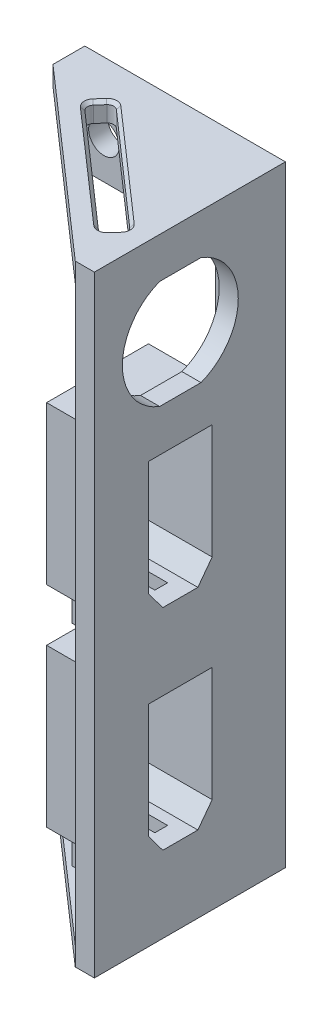
SolidWorks part; units mm, degrees
note: The reader was unsure of these and kept them because the rebuilt part matched: shared geometry of "Sketch4<10>".
ref_plane "Front Plane" through (0, 0, 0) normal (0, 0, 1) x (1, 0, 0)
ref_plane "Top Plane" through (0, 0, 0) normal (0, 1, 0) x (1, 0, 0)
ref_plane "Right Plane" through (0, 0, 0) normal (1, 0, 0) x (0, 0, -1)
sketch "Sketch4" plane through (0, 0, 0) normal (0, 0, 1) x (1, 0, 0)
  line L0 (68.7799, 0) -> (146.409, 0) construction
  line L2 (100.57, 12.5) -> (115.57, 12.5) construction
  line L11 (115.57, -12.5) -> (100.57, -12.5) construction
  line L12 (130.57, -45) -> (130.57, 0)
  line L13 (102.07, -34) -> (125.57, -34)
  line L14 (102.07, -34) -> (102.07, -48)
  line L15 (102.07, -48) -> (121.6669, -48)
  line L17 (121.6669, -48) -> (133.57, -48)
  line L19 (125.57, 0) -> (133.57, 0)
  line L20 (133.57, -48) -> (133.57, 0)
  line L21 (102.07, -45) -> (130.57, -45)
  line L25 (125.57, -34) -> (125.57, 0)
  line L26 (115.57, 12.5) -> (115.57, -12.5) construction
  circle A6 centre (108.07, -40) radius 2.4
  dimension "D1" = 4.8
  dimension "D2" = 3
  dimension "D5" = 6
  dimension "D6" = 6
  dimension "D8" = 5
  dimension "D4" = 5
  dimension "D3" = 3
  dimension "D7" = 10
extrude "Boss-Extrude4" add sketch "Sketch4" along normal blind 3 contours L25 L13 L14 L21 L12 L19 A6
extrude "Boss-Extrude5" add sketch "Sketch4<10>" along normal blind 30 contours L21 L14 L15 L17 L20 L19 L12
sketch "Sketch4<10>" plane through (0, 0, 0) normal (0, 0, 1) x (1, 0, 0) same geometry as "Sketch4"
sketch "Sketch11" plane through (0, -45, 0) normal (0, 1, 0) x (1, 0, 0)
  line L1 (102.07, -3) -> (125.57, -3) construction
  line L3 (130.57, -30) -> (130.57, -3) construction
  line L4 (102.07, -30) -> (130.57, -30) construction
  line L5 (130.57, -30) -> (102.07, -30)
  line L6 (102.07, -30) -> (102.07, -3) construction
  line L7 (102.07, -30) -> (102.07, -3)
  line L8 (130.57, -30) -> (102.07, -5)
  line M4 (102.07, -30) -> (130.57, -30)
  dimension "D1" = 2
extrude "Cut-Extrude2" cut sketch "Sketch11" against normal up to surface (3 mm away) and the other way through all contours L8 L7 M4 up to face at (117.82, -48, 15)
ref_plane "Mirror plane" through (0, 0, 0) normal (0, 1, 0) x (1, 0, 0)
mirror "Mirror2" about plane through (0, 0, 0) normal (0, 1, 0) of "Cut-Extrude2", "Boss-Extrude5", "Boss-Extrude4"
sketch "Socket holes" plane through (130.57, 0, 0) normal (-1, 0, 0) x (0, 0, 1)
  line L0 (11.5, -15) -> (11.5, -33)
  line L1 (11.5, -33) -> (13.75, -36)
  line L2 (13.75, -36) -> (19.25, -36)
  line L3 (19.25, -36) -> (21.5, -33)
  line L4 (21.5, -33) -> (21.5, -15)
  line L5 (21.5, -15) -> (11.5, -15)
  line L6 (16.5, 28.4966) -> (16.5, -28.9107) construction
  line L7 (13.2504, 41.6) -> (19.7496, 41.6)
  line L8 (13.2504, 24.6) -> (19.7496, 24.6)
  line L9 (7.3656, 33.1) -> (29.6735, 33.1) construction
  line L10 (30, 0) -> (24.5, 0) construction
  line L11 (3, -45) -> (3, 45) construction
  line L12 (8.5, -12) -> (8.5, -34)
  line L13 (8.5, -34) -> (12.25, -39)
  line L14 (30, -45) -> (30, 45) construction
  line L15 (3, -34) -> (3, 34) construction
  line L16 (7.833, 24) -> (20.4785, 24) construction
  line L17 (12.25, -39) -> (20.75, -39)
  line L18 (20.75, -39) -> (24.5, -34)
  line L19 (24.5, -34) -> (24.5, -12)
  line L20 (24.5, -12) -> (8.5, -12)
  line L21 (12.25, -39) -> (12.25, -43)
  line L22 (12.25, -43) -> (20.75, -43)
  line L23 (20.75, -43) -> (20.75, -39)
  line L36 (11.5, 0) -> (3, 0) construction
  line L37 (8.5, 21) -> (24.5, 21)
  line L38 (24.5, 21) -> (24.5, -1)
  line L39 (24.5, -1) -> (21.5, -6)
  line L40 (21.5, -6) -> (11.5, -6)
  line L41 (11.5, -6) -> (8.5, -1)
  line L42 (8.5, -1) -> (8.5, 21)
  line L43 (11.5, 18) -> (11.5, 0)
  line L44 (11.5, 0) -> (13.75, -3)
  line L45 (13.75, -3) -> (19.25, -3)
  line L46 (19.25, -3) -> (21.5, 0)
  line L47 (21.5, 0) -> (21.5, 18)
  line L48 (21.5, 18) -> (11.5, 18)
  line L49 (55, 0) -> (-55, 0) construction
  line L50 (11.5, -10) -> (21.5, -10)
  circle A0 centre (16.5, 33.1) radius 9.1
  point P18 (16.5, -36)
  dimension "D2" = 18.2
  dimension "D8" = 24
  dimension "D1" = 10
  dimension "D3" = 17
  dimension "D4" = 21
  dimension "D5" = 18
  dimension "D6" = 5.5
  dimension "D7" = 3
  dimension "D9" = 15
  dimension "D10" = 4
  dimension "D11" = 21
  dimension "D12" = 10
  dimension "D13" = 18
  dimension "D14" = 5.5
  dimension "D15" = 6
  dimension "D16" = 3
  dimension "D17" = 3
  dimension "D18" = 3
  dimension "D19" = 3
  dimension "D20" = 5
  dimension "D21" = 22
  dimension "D22" = 4
extrude "socketholes" cut sketch "Socket holes" against normal up to surface (3 mm away) contours L4 L5 L0 L1 L2 L3 | L7 A0 L8 | L48 L43 L44 L45 L46 L47 up to face at (133.57, 0, 15)
sketch "Sketch12" plane through (0, -48, 0) normal (0, -1, 0) x (1, 0, 0)
  line L0 (130.57, 30) -> (130.57, 0) construction
  line L1 (102.07, 0) -> (133.57, 0) construction
  line L2 (102.07, 5) -> (133.57, 5) construction
  line L3 (133.57, 30) -> (133.57, 0) construction
  line L4 (106.6193, 5) -> (130.57, 26.0094) construction
  line L5 (102.07, 5) -> (130.57, 30) construction
  line L6 (109.6188, 7.6312) -> (128.262, 23.9848)
  line L7 (109.6188, 7.6312) -> (111.9269, 5)
  line L8 (128.262, 23.9848) -> (130.57, 21.3536)
  line L9 (111.9269, 5) -> (130.57, 21.3536)
  dimension "D1" = 3
  dimension "D2" = 3.5
extrude "Cut-Extrude4" cut sketch "Sketch12" against normal blind 110 contours L9 L8 L6 L7
fillet "Fillet1" radius 1 8 edges at (109.6188, 46.5, 7.6312) (111.9269, 46.5, 5) (130.57, 46.5, 21.3536) (128.262, 46.5, 23.9848) (111.9269, -46.5, 5) (109.6188, -46.5, 7.6312) (128.262, -46.5, 23.9848) (130.57, -46.5, 21.3536)
chamfer "Chamfer1" distance 0.5 angle 45 16 edges at (118.9404, 48, 15.808) (128.2349, 48, 23.5714) (110.0322, 48, 7.6041) (129.416, 48, 22.6692) (110.7729, 48, 6.3156) (130.1567, 48, 21.3807) (111.9539, 48, 5.4133) (121.2484, 48, 13.1768) (118.9404, -48, 15.808) (110.0322, -48, 7.6041) (128.2349, -48, 23.5714) (110.7729, -48, 6.3156) (129.416, -48, 22.6692) (111.9539, -48, 5.4133) (130.1567, -48, 21.3807) (121.2484, -48, 13.1768)
sketch "Sketch14" plane through (130.57, 0, 0) normal (-1, 0, 0) x (0, 0, 1)
  line L19 (8.5, -1) -> (8.5, -11)
  line L20 (8.5, -11) -> (24.5, -11)
  line L22 (24.5, -44) -> (8.5, -44)
  line L24 (24.5, -34) -> (24.5, -44)
  line L25 (13.75, -36) -> (19.25, -36) construction
  line L26 (8.5, -34) -> (8.5, -44)
  line L27 (20.75, -39) -> (24.5, -34)
  line L28 (12.25, -39) -> (20.75, -39)
  line L29 (8.5, -34) -> (12.25, -39)
  line L30 (8.5, -12) -> (8.5, -34)
  line L31 (24.5, -12) -> (8.5, -12)
  line L32 (24.5, -34) -> (24.5, -12)
  line L33 (20.75, -39) -> (24.5, -34) construction
  line L35 (8.5, -34) -> (12.25, -39) construction
  line L36 (8.5, -12) -> (8.5, -34)
  line L37 (24.5, -12) -> (8.5, -12)
  line L38 (24.5, -34) -> (24.5, -12)
  line L40 (24.5, -11) -> (24.5, -1)
  line L41 (13.75, -3) -> (19.25, -3) construction
  line L42 (11.5, 18) -> (11.5, 0)
  line L43 (8.5, -1) -> (11.35, -4.8)
  line L44 (21.65, -4.8) -> (24.5, -1)
  line L45 (24.5, 21) -> (8.5, 21)
  line L46 (8.5, 21) -> (8.5, -1)
  line L47 (24.5, -1) -> (24.5, 21)
  line L48 (11.5, 0) -> (13.75, -3)
  line L49 (13.75, -3) -> (19.25, -3)
  line L50 (24.5, 21) -> (8.5, 21)
  line L51 (8.5, 21) -> (8.5, -1)
  line L52 (24.5, -1) -> (24.5, 21)
  line L53 (19.25, -3) -> (21.5, 0)
  line L54 (21.5, 0) -> (21.5, 18)
  line L55 (21.5, 18) -> (11.5, 18)
  dimension "D3" = 3
  dimension "D2" = 8
  dimension "D4" = 8
  dimension "D1" = 3
extrude "Boss-Extrude6" add sketch "Sketch14" along normal blind 10
sketch "Sketch15" plane through (120.57, 0, 0) normal (-1, 0, 0) x (0, 0, 1)
  line L0 (16.5, -36) -> (16.5, -44) construction
  line L1 (19.25, -36) -> (13.75, -36) construction
  line L2 (24.5, -44) -> (8.5, -44) construction
  line L3 (17.5, -36) -> (17.5, -44)
  line L4 (15.5, -36) -> (15.5, -44)
  line L5 (16.5, -10.7141) -> (16.5, -2.7141) construction
  line L7 (15.5, -10.7141) -> (15.5, -2.7141)
  line L8 (17.5, -10.7141) -> (17.5, -2.7141)
  arc A0 (17.5, -36) -> (15.5, -36) centre (16.5, -36) ccw
  arc A1 (15.5, -44) -> (17.5, -44) centre (16.5, -44) ccw
  arc A2 (15.5, -10.7141) -> (17.5, -10.7141) centre (16.5, -10.7141) ccw
  arc A3 (17.5, -2.7141) -> (15.5, -2.7141) centre (16.5, -2.7141) ccw
  point P6 (16.5, -40)
  point P15 (16.5, -6.7141)
  dimension "D1" = 1
extrude "Cut-Extrude5" cut sketch "Sketch15" against normal up to surface (10 mm away) up to face at (130.57, 0, 18.1179)
chamfer "Chamfer2" distance 1 angle 45 14 edges at (120.57, -36, 18.375) (120.57, -36, 14.625) (120.57, -34.5, 12.625) (120.57, -24, 11.5) (120.57, -15, 16.5) (120.57, -24, 21.5) (120.57, -34.5, 20.375) (120.57, -3, 18.375) (120.57, -3, 14.625) (120.57, -1.5, 12.625) (120.57, 9, 11.5) (120.57, 18, 16.5) (120.57, 9, 21.5) (120.57, -1.5, 20.375)
sketch "Sketch18" plane through (0, 0, 24.5) normal (0, 0, 1) x (1, 0, 0)
  line L0 (120.57, -44) -> (130.57, -36) construction
  line L1 (130.57, -12) -> (130.57, -44) construction
  line L2 (120.57, -11) -> (130.57, -3) construction
  line L3 (130.57, -45) -> (130.57, 45) construction
  line L4 (120.57, -11) -> (130.57, -11) construction
  circle A0 centre (125.57, -40) radius 1.8
  circle A1 centre (125.57, -7) radius 1.8
  dimension "D2" = 3.6
  dimension "D3" = 3.6
  dimension "D1" = 8
  dimension "D4" = 8
extrude "Cut-Extrude7" cut sketch "Sketch18" against normal blind 17
sketch "Sketch19" plane through (0, 0, 24.5) normal (0, 0, 1) x (1, 0, 0)
  line L0 (125.57, -36.75) -> (120.57, -36.75)
  line L1 (120.57, -12) -> (120.57, -44) construction
  line L2 (128.82, -40) -> (128.82, -44)
  line L3 (120.57, -44) -> (130.57, -44) construction
  line L4 (128.82, -44) -> (120.57, -44)
  line L5 (120.57, -44) -> (120.57, -36.75)
  line L6 (125.57, -3.75) -> (120.57, -3.75)
  line L7 (120.57, -11) -> (120.57, 21) construction
  line L8 (120.57, -3.75) -> (120.57, -11)
  line L9 (120.57, -11) -> (128.82, -11)
  line L10 (120.57, -11) -> (130.57, -11) construction
  line L11 (128.82, -11) -> (128.82, -7)
  circle A0 centre (125.57, -40) radius 3.25
  arc A1 (128.82, -7) -> (125.57, -3.75) centre (125.57, -7) ccw
  dimension "D1" = 6.5
  dimension "D2" = 6.5
extrude "Cut-Extrude8" cut sketch "Sketch19" against normal blind 4
